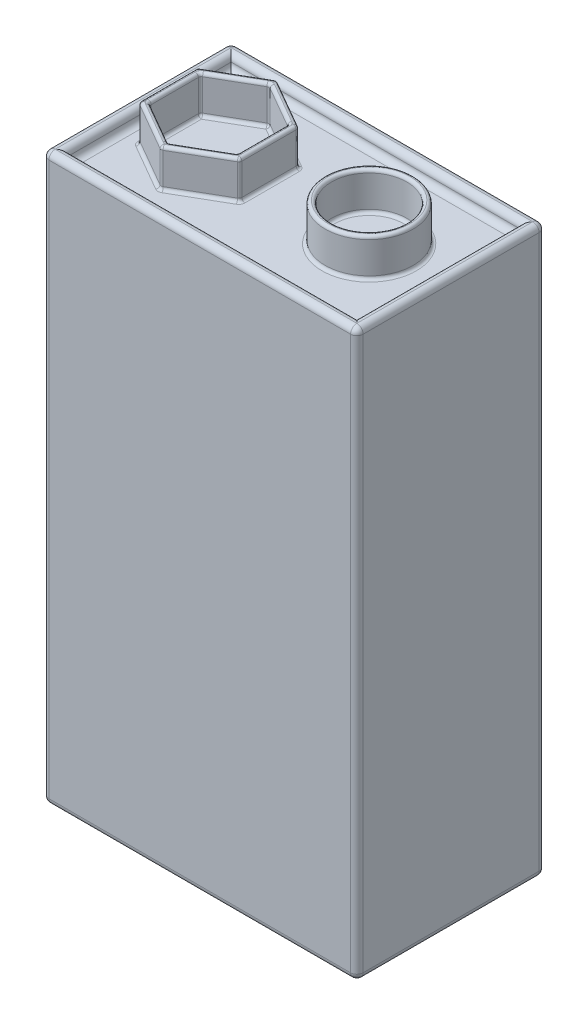
SolidWorks part; units mm, degrees
ref_plane "Front Plane" through (0, 0, 0) normal (0, 0, 1) x (1, 0, 0)
ref_plane "Top Plane" through (0, 0, 0) normal (0, 1, 0) x (1, 0, 0)
ref_plane "Right Plane" through (0, 0, 0) normal (1, 0, 0) x (0, 0, -1)
sketch "Sketch1" plane through (0, 0, 0) normal (0, 0, 1) x (1, 0, 0)
  line L1 (-12.5, 22.5) -> (12.5, 22.5)
  line L2 (-12.5, 22.5) -> (-12.5, -22.5)
  line L3 (-12.5, -22.5) -> (12.5, -22.5)
  line L4 (12.5, 22.5) -> (12.5, -22.5)
  line L5 (0, -22.5) -> (0, 22.5) construction
  line L6 (-12.5, 0) -> (12.5, 0) construction
  point P0 (0, 0)
extrude "Boss-Extrude1" add sketch "Sketch1" along normal blind 15
sketch "Sketch2" plane through (0, 22.5, 0) normal (0, 1, 0) x (1, 0, 0)
  line L1 (11.5, -1) -> (-11.5, -1)
  line L2 (-11.5, -1) -> (-11.5, -14)
  line L3 (-11.5, -14) -> (11.5, -14)
  line L4 (11.5, -14) -> (11.5, -1)
extrude "Cut-Extrude1" cut sketch "Sketch2" against normal blind 1
sketch "Sketch3" plane through (0, -22.5, 0) normal (0, -1, 0) x (1, 0, 0)
  line L0 (-11.5, 1) -> (11.5, 1)
  line L1 (11.5, 1) -> (11.5, 14)
  line L2 (11.5, 14) -> (-11.5, 14)
  line L3 (-11.5, 14) -> (-11.5, 1)
  line L4 (-12.5, 0) -> (12.5, 0)
  line L5 (12.5, 0) -> (12.5, 15)
  line L6 (12.5, 15) -> (-12.5, 15)
  line L7 (-12.5, 15) -> (-12.5, 0)
  line L8 (-12.5, 0) -> (12.5, 0) construction
  line L9 (12.5, 0) -> (12.5, 15) construction
  line L10 (12.5, 15) -> (-12.5, 15) construction
  line L11 (-12.5, 15) -> (-12.5, 0) construction
  dimension "D1" = 0
  dimension "D2" = 1
extrude "Cut-Extrude2" cut sketch "Sketch3" against normal blind 1
fillet "Fillet2" radius 0.5 28 edges at (12.5, 22.5, 7.5) (0, 22.5, 15) (-12.5, 22.5, 7.5) (0, 22.5, 0) (-11.5, 22.5, 7.5) (0, 22.5, 14) (11.5, 22.5, 7.5) (0, 22.5, 1) (0, 21.5, 14) (-11.5, 21.5, 7.5) (0, 21.5, 1) (11.5, 21.5, 7.5) (-12.5, -22.5, 7.5) (0, -22.5, 15) (12.5, -22.5, 7.5) (0, -22.5, 0) (11.5, -22.5, 7.5) (0, -22.5, 14) (-11.5, -22.5, 7.5) (0, -22.5, 1) (0, -21.5, 14) (11.5, -21.5, 7.5) (0, -21.5, 1) (-11.5, -21.5, 7.5) (12.5, 0, 15) (-12.5, 0, 15) (-12.5, 0, 0) (12.5, 0, 0)
sketch "Sketch4" plane through (0, 21.5, 0) normal (0, 1, 0) x (1, 0, 0)
  line L0 (-6, -12.1079) -> (-2, -9.7985)
  line L1 (-6, -11.5306) -> (-2.5, -9.5099)
  line L2 (-2.5, -9.5099) -> (-2.5, -5.4684)
  line L3 (-2.5, -5.4684) -> (-6, -3.4477)
  line L4 (-6, -3.4477) -> (-9.5, -5.4684)
  line L5 (-9.5, -5.4684) -> (-9.5, -9.5099)
  line L6 (-9.5, -9.5099) -> (-6, -11.5306)
  line L7 (-2, -9.7985) -> (-2, -5.1797)
  line L8 (-2, -5.1797) -> (-6, -2.8703)
  line L9 (-6, -2.8703) -> (-10, -5.1797)
  line L10 (-10, -5.1797) -> (-10, -9.7985)
  line L11 (-10, -9.7985) -> (-6, -12.1079)
  circle A0 centre (6, -7.52) radius 3
  circle A1 centre (-6, -7.4891) radius 3.5 construction
  circle A2 centre (6, -7.52) radius 3.5
  dimension "D1" = 7
  dimension "D2" = 6
  dimension "D3" = 6
  dimension "D4" = 6
  dimension "D5" = 0.5
extrude "Boss-Extrude2" add sketch "Sketch4" along normal blind 3
fillet "Fillet3" radius 0.25 40 edges at (-8, 21.5, 10.9532) (-7.75, 21.5, 4.4581) (-2, 21.5, 7.4891) (-7.75, 21.5, 10.5202) (-6, 23, 11.5306) (-4.25, 21.5, 10.5202) (-6, 23, 3.4477) (-4.25, 21.5, 4.4581) (-2.5, 23, 5.4684) (-2.5, 23, 9.5099) (-2.5, 21.5, 7.4891) (-9.5, 23, 9.5099) (-9.5, 23, 5.4684) (-9.5, 21.5, 7.4891) (-8, 21.5, 4.025) (-2, 23, 5.1797) (-6, 23, 2.8703) (-4, 21.5, 4.025) (-10, 23, 5.1797) (-10, 23, 9.7985) (-10, 21.5, 7.4891) (-6, 23, 12.1079) (-2, 23, 9.7985) (-4, 21.5, 10.9532) (3, 21.5, 7.52) (3, 24.5, 7.52) (2.5, 24.5, 7.52) (-2.5, 24.5, 7.4891) (-4.25, 24.5, 4.4581) (-7.75, 24.5, 4.4581) (-9.5, 24.5, 7.4891) (-7.75, 24.5, 10.5202) (-4.25, 24.5, 10.5202) (-10, 24.5, 7.4891) (-8, 24.5, 4.025) (-4, 24.5, 4.025) (-2, 24.5, 7.4891) (-4, 24.5, 10.9532) (-8, 24.5, 10.9532) (2.5, 21.5, 7.52)
